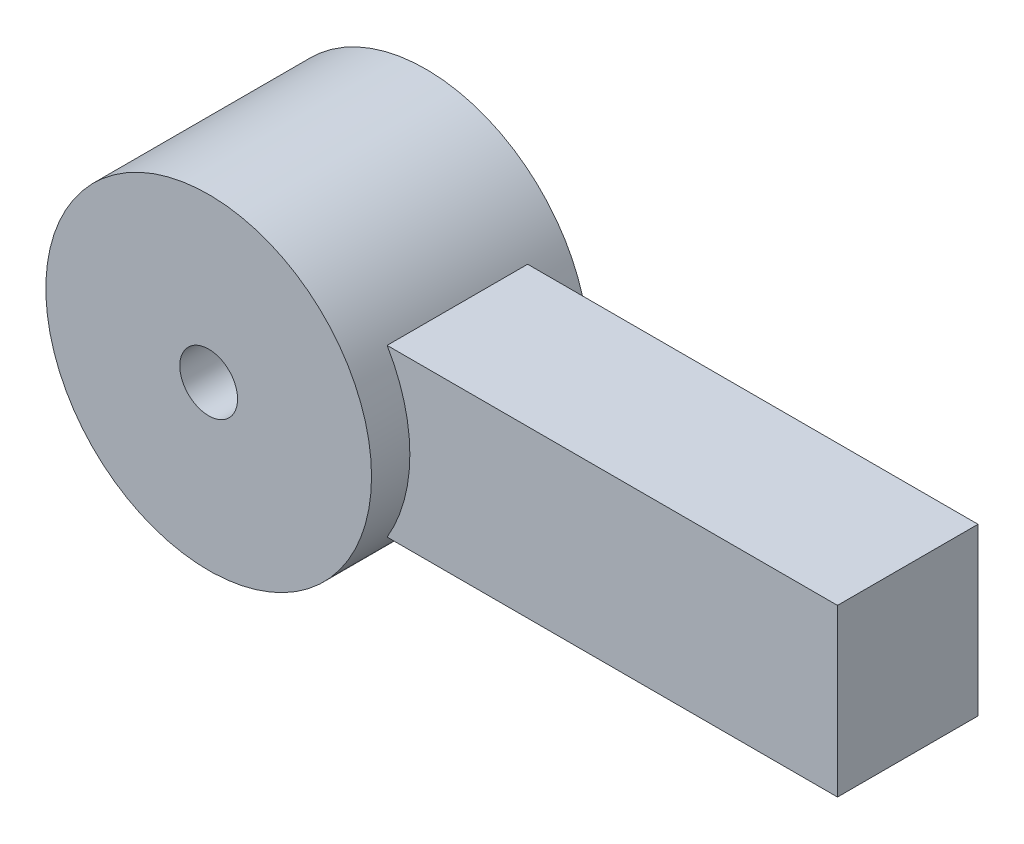
SolidWorks part; units mm, degrees
ref_plane "Front" through (0, 0, 0) normal (0, 0, 1) x (1, 0, 0)
ref_plane "Top" through (0, 0, 0) normal (0, 1, 0) x (1, 0, 0)
ref_plane "Right" through (0, 0, 0) normal (1, 0, 0) x (0, 0, -1)
sketch "Sketch1" plane through (0, 0, 0) normal (0, 0, 1) x (1, 0, 0)
  line L0 (0, 0) -> (57.5688, 0) construction
  line L1 (46.2262, -6.4982) -> (10.9688, -6.4982)
  line L2 (46.2262, -6.4982) -> (46.2262, 6.4982)
  line L3 (46.2262, 6.4982) -> (10.9688, 6.4982)
  line L5 (46.2262, -6.4982) -> (10.9688, 6.4982) construction
  line L6 (46.2262, 6.4982) -> (10.9688, -6.4982) construction
  line L7 (19.4744, -6.4982) -> (19.4744, 6.4982) construction
  circle A0 centre (0, 0) radius 12.7492
  circle A1 centre (0, 0) radius 2.2616
  point P3 (28.5975, 0)
extrude "Boss-Extrude1" add sketch "Sketch1" along normal mid plane 11 contours A0 L1 L2 L3 region at (29.1958, 0, 0)
extrude "Boss-Extrude2" add sketch "Sketch1<3>" along normal mid plane 17 contours A0 A1 region at (-12.3886, 0, 0)
sketch "Sketch1<3>" plane through (0, 0, 0) normal (0, 0, 1) x (1, 0, 0) same geometry as "Sketch1"
